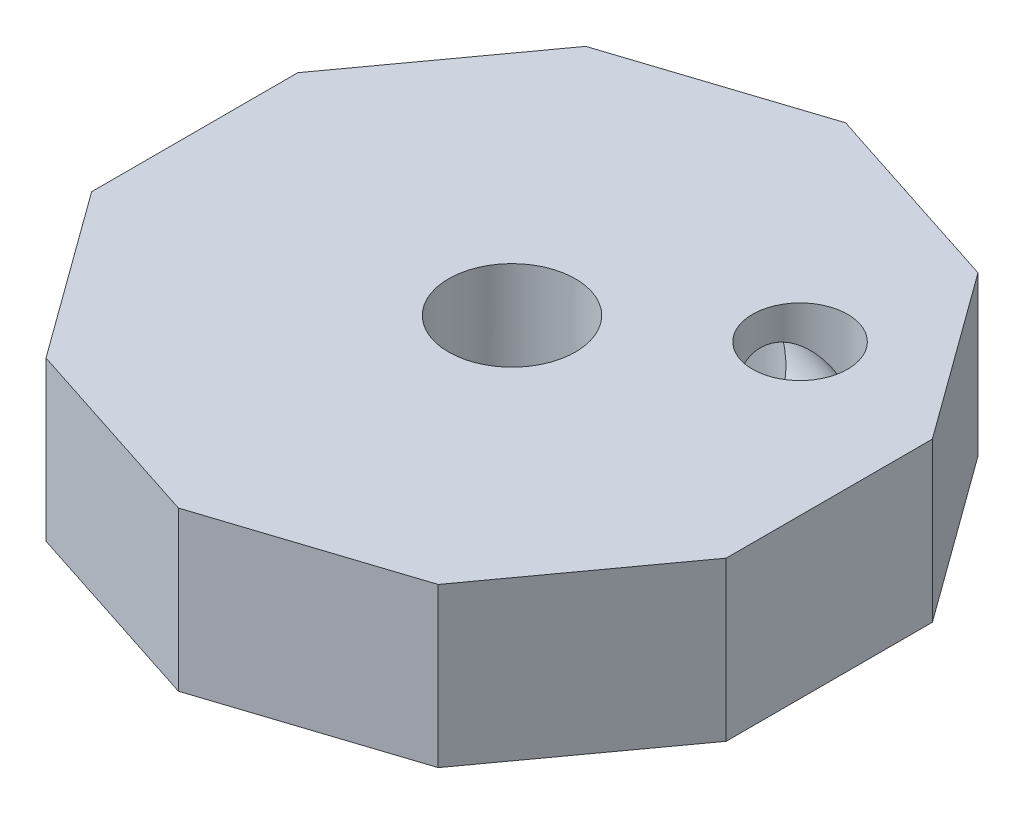
SolidWorks part; units mm, degrees
ref_plane "Front Plane" through (0, 0, 0) normal (0, 0, 1) x (1, 0, 0)
ref_plane "Top Plane" through (0, 0, 0) normal (0, 1, 0) x (1, 0, 0)
ref_plane "Right Plane" through (0, 0, 0) normal (1, 0, 0) x (0, 0, -1)
sketch "Sketch1" plane through (0, 0, 0) normal (0, 1, 0) x (1, 0, 0)
  line L0 (6.1803, -8.5065) -> (10, -3.2492)
  line L1 (0, 10.5146) -> (-6.1803, 8.5065)
  line L2 (-6.1803, 8.5065) -> (-10, 3.2492)
  line L3 (-10, 3.2492) -> (-10, -3.2492)
  line L4 (-10, -3.2492) -> (-6.1803, -8.5065)
  line L5 (-6.1803, -8.5065) -> (0, -10.5146)
  line L6 (0, -10.5146) -> (6.1803, -8.5065)
  line L7 (10, -3.2492) -> (10, 3.2492)
  line L8 (10, 3.2492) -> (6.1803, 8.5065)
  line L9 (6.1803, 8.5065) -> (0, 10.5146)
  circle A0 centre (0, 0) radius 10 construction
  dimension "D1" = 20
extrude "Boss-Extrude1" add sketch "Sketch1" along normal blind 5
sketch "Sketch2" plane through (0, 5, 0) normal (0, 1, 0) x (1, 0, 0)
  line L0 (8.0902, 5.8779) -> (0, 0) construction
  line L1 (10, 3.2492) -> (6.1803, 8.5065) construction
  circle A0 centre (0, 0) radius 2
  circle A1 centre (5.2586, 3.8206) radius 1.5
  dimension "D1" = 4
  dimension "D2" = 3
  dimension "D3" = 3.5
extrude "Cut-Extrude1" cut sketch "Sketch2" against normal blind 5 contours A1 L0 | L0 A1 | A0 region at (5.6328, 5, -3.3056) region at (4.8844, 5, -4.3356)
sketch "Sketch4" plane through (0, 0, 0) normal (0, -1, 0) x (1, 0, 0)
  circle A0 centre (0, 0) radius 3
  dimension "D1" = 6
extrude "Cut-Extrude2" cut sketch "Sketch4" against normal blind 1.5
sketch "Sketch5" plane through (0, 5, 0) normal (0, 1, 0) x (1, 0, 0)
  line L0 (5.2586, 3.8206) -> (1.4544, 5.0567)
  line L1 (5.2586, 3.8206) -> (5.2586, -0.1794)
  line L2 (5.2586, 3.8206) -> (8.0902, 5.8779) construction
  line L3 (10, 3.2492) -> (6.1803, 8.5065) construction
  line L4 (5.2586, 3.8206) -> (7.6654, 0.5079) construction
  line L5 (5.2586, 3.8206) -> (2.0521, 8.234) construction
  line L7 (1.4544, 5.0567) -> (1.9179, 6.4833)
  line L8 (1.4544, 5.0567) -> (0.9909, 3.6301)
  circle A0 centre (1.4544, 5.0567) radius 1.5
  circle A1 centre (5.2586, 3.8206) radius 1.5
  circle A2 centre (5.2586, 3.8206) radius 1.5
  circle A3 centre (5.2586, -0.1794) radius 1.5
  dimension "D4" = 4
  dimension "D6" = 3
  dimension "D7" = 3
  dimension "D2" = 144
  dimension "D3" = 36
  dimension "D5" = 4
  dimension "D8" = 90
  dimension "D9" = 90
  dimension "D1" = 0
sketch "Sketch11" plane through (0, 0, 0) normal (0, -1, 0) x (1, 0, 0)
  circle A1 centre (1.4544, -5.0567) radius 1.5 construction
  circle A3 centre (1.4544, -5.0567) radius 1.5
ref_plane "Plane3" through (5.2586, 0, 0) normal (-1, 0, 0) x (0, 0, 1)
ref_plane "Plane4" through (1.625, 0, -5.0012) normal (0.309, 0, -0.9511) x (-0.9511, 0, -0.309)
sketch "Sketch12" plane through (1.625, 0, -5.0012) normal (0.309, 0, -0.9511) x (-0.9511, 0, -0.309)
  line L0 (-1.3206, 0) -> (1.6794, 0) construction
  line L1 (1.6794, 5) -> (-1.3206, 5) construction
  line L2 (-1.3206, 0) -> (1.6794, 0)
  line L3 (1.6794, 5) -> (-1.3206, 5)
  line L4 (0.1794, 0) -> (0.1794, 2.4992)
  line L5 (-3.8206, 5) -> (0.1794, 5) construction
  line L6 (-3.8206, 5) -> (0.1794, 5)
  line L8 (0.1794, 2.4992) -> (-3.8206, 2.4992)
sweep "Cut-Sweep5" cut profiles "Sketch11" path "Sketch12"
sketch "Sketch17" plane through (0, 0, 0) normal (0, -1, 0) x (1, 0, 0)
  circle A0 centre (5.2586, 0.1794) radius 1.5 construction
  circle A1 centre (5.2586, 0.1794) radius 1.5
sketch "Sketch18" plane through (5.2586, 0, 0) normal (-1, 0, 0) x (0, 0, 1)
  line L0 (-3.8206, 5) -> (0.1794, 5) construction
  line L1 (-1.3206, 0) -> (1.6794, 0) construction
  line L2 (1.6794, 5) -> (-1.3206, 5) construction
  line L3 (-3.8206, 5) -> (0.1794, 5)
  line L4 (-1.3206, 0) -> (1.6794, 0)
  line L5 (1.6794, 5) -> (-1.3206, 5)
  line L6 (0.1794, 0) -> (0.1794, 2.5)
  line L7 (0.1794, 2.5) -> (-3.8206, 2.5)
  dimension "D1" = 2.5
sweep "Cut-Sweep6" cut profiles "Sketch17" path "Sketch18"
